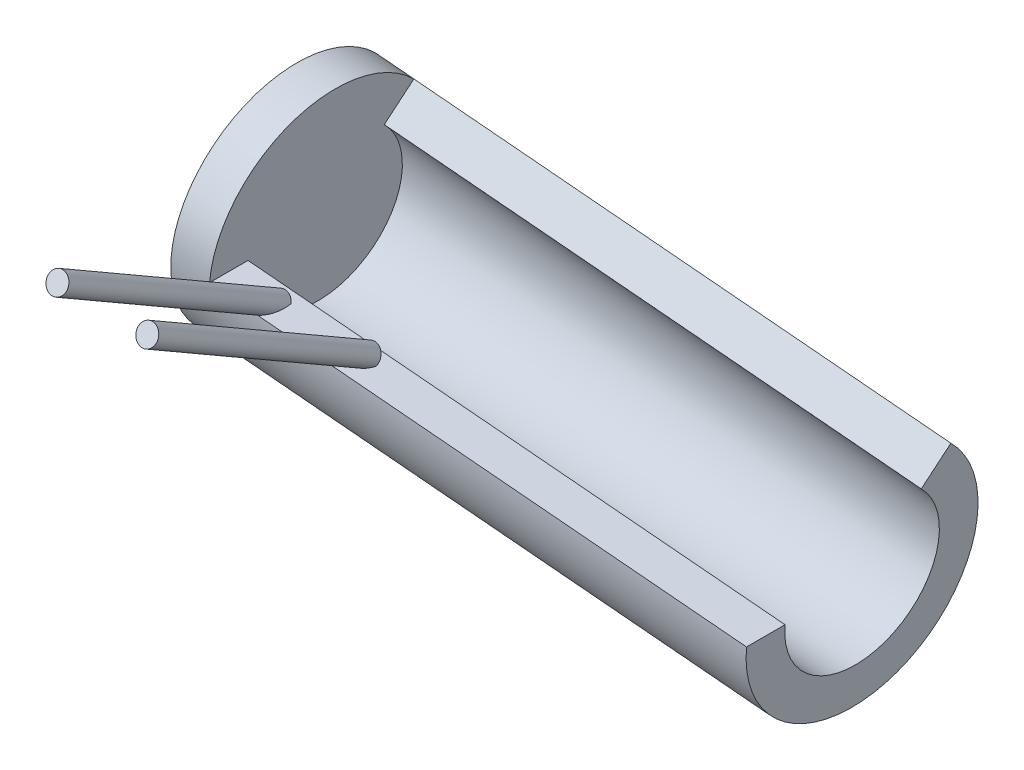
SolidWorks part; units mm, degrees
ref_plane "Front Plane" through (0, 0, 0) normal (0, 0, 1) x (1, 0, 0)
ref_plane "Top Plane" through (0, 0, 0) normal (0, 1, 0) x (1, 0, 0)
ref_plane "Right Plane" through (0, 0, 0) normal (1, 0, 0) x (0, 0, -1)
ref_axis "Axis1" through (88.99, 0, 0) along (-1, 0, 0)
ref_plane "Plane1" through (0, 0, 0) normal (0, 0.5, -0.866) x (-1, 0, 0)
sketch "Sketch2" plane through (0, 0, 0) normal (0, 0.5, -0.866) x (-1, 0, 0)
  line L0 (0, 0) -> (-17.5, 0)
  line L1 (-88.99, 0) -> (88.99, 0) construction
  line L2 (0, 55) -> (0, -55) construction
  circle A0 centre (-17.5, 0) radius 4
  circle A1 centre (17.5, 0) radius 4
extrude "Boss-Extrude1" add sketch "Sketch2" along normal blind 100 contours A1 | A0 region at (21.3869, 0, 0) region at (-17.5, 0, 0)
ref_axis "Axis2" through (0, 0, -93.1327) along (0, 0, 1)
ref_plane "Plane2" through (0, 0, 0) normal (-0.9962, 0.0872, 0) x (0, 0, 1)
sketch "Sketch4" plane through (0, 0, 0) normal (-0.9962, 0.0872, 0) x (0, 0, 1)
  line L1 (-93.1327, 0) -> (6.5301, 0) construction
  line L5 (-7.4098, 42.4264) -> (-7.5009, 42.5175)
  line L8 (80.0283, 0) -> (65.0283, 0)
  line L9 (3.1885, 31.8281) -> (13.7951, 21.2215)
  arc A6 (3.1885, 31.8281) -> (80.0283, 0) centre (35.0166, 0) ccw
  arc A7 (13.7951, 21.2215) -> (65.0283, 0) centre (35.0166, 0) ccw
extrude "Boss-Extrude3" add sketch "Sketch4" against normal blind 175 and the other way blind 50 contours A7 L8 A6 L9
sketch "Sketch5" plane through (-49.8097, 4.3578, 0) normal (-0.9962, 0.0872, 0) x (0, 0, 1)
  circle A3 centre (35.0166, 0) radius 45.0117
extrude "Boss-Extrude4" add sketch "Sketch5" against normal blind 15
sketch "Sketch7" plane through (174.3341, -15.2523, 0) normal (0.9962, -0.0872, 0) x (0, 0, -1)
  line L2 (-35.0166, -30.0117) -> (-35.0166, 0)
  arc A0 (-65.0283, 0) -> (-13.7951, 21.2215) centre (-35.0166, 0) ccw construction
ref_axis "Axis3" through (171.7184, -45.1498, 35.0166) along (0.0872, 0.9962, 0)
ref_plane "Plane3" through (174.3341, -15.2523, 0) normal (0.9962, -0.0872, 0) x (0.0872, 0.9962, 0)
ref_plane "Plane4" through (0, 0, 35.0166) normal (0, 0, -1) x (0.0872, 0.9962, 0)
mirror "Mirror2" about plane through (0, 0, 35.0166) normal (0, 0, -1) of "Boss-Extrude1"
sketch "Sketch8" plane through (174.3341, -15.2523, 0) normal (0.9962, -0.0872, 0) x (0, 0, -1)
  line L1 (-80.0283, 0) -> (-208.367, 0)
  line L3 (-35.0166, 45.0117) -> (-35.0166, 173.3504)
  circle A3 centre (-35.0166, 0) radius 30.0117
  arc A4 (-80.0283, 0) -> (-35.0166, 45.0117) centre (-35.0166, 0) ccw
  arc A5 (-208.367, 0) -> (-35.0166, 173.3504) centre (-35.0166, 0) ccw
extrude "Cut-Extrude1" cut sketch "Sketch8" against normal up to surface (210 mm away) up to face at (-33.9869, 13.1078, 39.1984)
